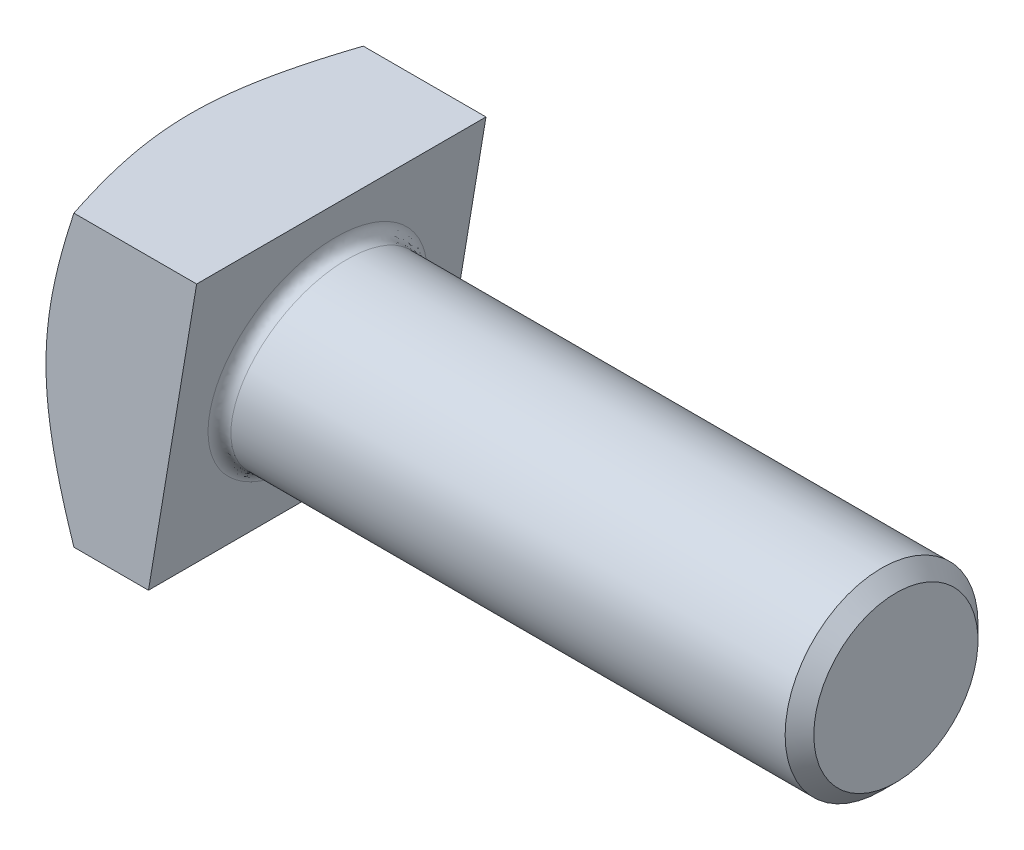
SolidWorks part; units mm, degrees
extrude "BaseHead" add sketch "Sketch1" along normal mid plane 38.1
sketch "Sketch1" plane through (0, 0, 0) normal (0, 0, 1) x (1, 0, 0)
  line L0 (0, -19.05) -> (0, 19.05)
  line L1 (0, 19.05) -> (19.8374, 19.05)
  line L2 (19.8374, 19.05) -> (13.4958, -19.05)
  line L3 (13.4958, -19.05) -> (0, -19.05)
  dimension "D1" = 19.05
  dimension "D2" = 80.55
ref_plane "Plane1" through (0, 0, 0) normal (0, 0, 1) x (1, 0, 0)
ref_plane "Plane2" through (0, 0, 0) normal (0, 1, 0) x (1, 0, 0)
ref_plane "Plane3" through (0, 0, 0) normal (1, 0, 0) x (0, 0, -1)
sketch "BodySke" plane through (0, 0, 0) normal (0, 0, 1) x (1, 0, 0)
  line L0 (0, 0) -> (0, 12.7)
  line L1 (0, 12.7) -> (90.9769, 12.7)
  line L2 (90.9769, 12.7) -> (92.8666, 10.8102)
  line L3 (92.8666, 10.8102) -> (92.8666, 0)
  line L4 (92.8666, 0) -> (0, 0)
  line L5 (0, -19.05) -> (0, 19.05) construction
  line L6 (0, 0) -> (101.6, 0) construction
  line L7 (90.9769, -12.7) -> (92.8666, -10.8102) construction
  line L8 (19.8374, 19.05) -> (13.4958, -19.05) construction
  line L9 (22.3774, 15.875) -> (22.3774, -3.175) construction
  line L10 (29.3666, 19.05) -> (29.3666, -3.175) construction
  point P11 (16.6666, 0)
  dimension "Diameter" = 25.4
  dimension "Advance" = 2.54
revolve "Body" add sketch "BodySke" angle 360 about L6
cosmetic thread "ThreadCosmetic" [suppressed] parameters "Thread_length"=63.5, "Thread_minor"=21.6205
ref_plane "Plane4" through (0, 0, 0) normal (0, -0.7071, 0.7071) x (1, 0, 0)
sketch "Sketch3" plane through (0, 0, 0) normal (0, -0.7071, 0.7071) x (1, 0, 0)
  line L0 (0, 19.05) -> (9.6016, 39.6408)
  line L1 (9.6016, 39.6408) -> (-6.35, 39.6408)
  line L2 (-6.35, 39.6408) -> (-6.35, 19.05)
  line L3 (-6.35, 19.05) -> (0, 19.05)
  line L4 (0, 0) -> (28.575, 0) construction
  line L5 (0, 0) -> (0, 26.9408) construction
  line L6 (-6.35, -19.05) -> (0, -19.05) construction
  line L7 (0, 26.9408) -> (19.8374, 26.9408) construction
  dimension "D1" = 38.1
  dimension "D2" = 65
  dimension "D3" = 6.35
  dimension "D4" = 12.7
revolve "HeadChamfer" cut sketch "Sketch3" angle 360 about L4
fillet "HeadFillet" radius 1.524 1 edges at (14.5528, -12.7, 0)
sketch "ThdSchSke" plane through (0, 0, 0) normal (0, 0, 1) x (1, 0, 0)
  line L0 (32.5374, -10.8102) -> (31.2142, -12.7)
  line L1 (32.5374, -10.8102) -> (33.8606, -12.7)
  line L2 (33.8606, -12.7) -> (33.8606, -15.875)
  line L3 (-3.175, 0) -> (5.1513, 0) construction
  line L5 (33.8606, -15.875) -> (31.2142, -15.875)
  line L6 (31.2142, -15.875) -> (31.2142, -12.7)
  dimension "Thread_minor" = 21.6205
  dimension "Diameter" = 25.4
  dimension "Start" = 32.5374
revolve "ThreadSchematic" [suppressed] cut sketch "ThdSchSke" angle 360 about L3
pattern_linear "ThdSchPat" [suppressed]
equation "\"D1@Sketch1\" = \"Width_flats@Sketch1\" / 2"
equation "\"D1@BaseHead\" = \"Width_flats@Sketch1\""
equation "\"Thread_minor@ThreadCosmetic\" = \"Minor_dia@BodySke\""
equation "\"D1@Sketch3\" =  \"Width_flats@Sketch1\""
equation "\"Thread_length@ThreadCosmetic\" = ((sgn( (\"Length@BodySke\" - \"Advance@BodySke\" ) - \"Thread_nom@BodySke\" )-1)*( (\"Length@BodySke\" - \"Advance@BodySke\" ) - \"Thread_nom@BodySke\" ))/-2+ \"Thread_nom@BodySke\""
equation "\"Thread_minor@ThdSchSke\" = \"Minor_dia@BodySke\""
equation "\"Diameter@ThdSchSke\" = \"Diameter@BodySke\""
equation "\"Overcut@ThdSchSke\" = \"Diameter@BodySke\" * 1.25"
equation "\"Start@ThdSchSke\" = \"Head_ht@Sketch1\" + \"Length@BodySke\" - \"Thread_length@ThreadCosmetic\"  '---Non-countersunk---"
equation "\"Num_threads@ThdSchPat\" = int( \"Thread_length@ThreadCosmetic\" / \"Advance@BodySke\" + 0.999 )  + 1"
equation "\"Advance@ThdSchPat\" = \"Thread_length@ThreadCosmetic\" /  (\"Num_threads@ThdSchPat\" - 1) 'relax it"
equation "\"Num_threads@ThdSchPat\" = \"Num_threads@ThdSchPat\" - sgn( \"Num_threads@ThdSchPat\" - 1) '---chamfered tips only---"
